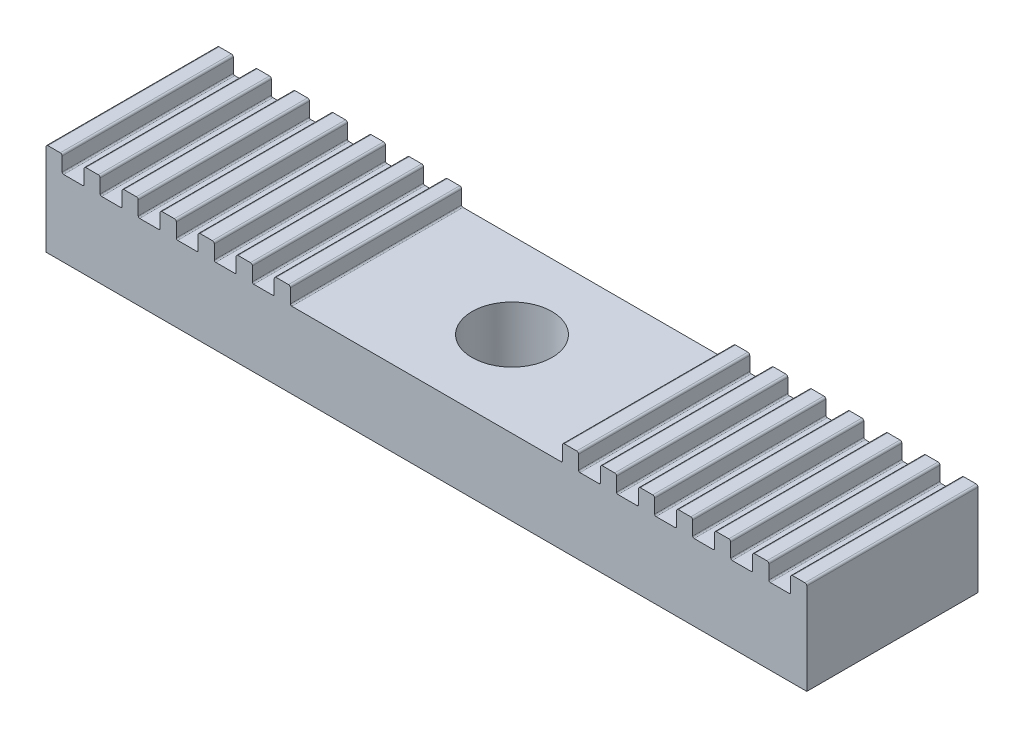
SolidWorks part; units mm, degrees
material "6061-T6 (SS)"
ref_plane "Front Plane" through (0, 0, 0) normal (0, 0, 1) x (1, 0, 0)
ref_plane "Top Plane" through (0, 0, 0) normal (0, 1, 0) x (1, 0, 0)
ref_plane "Right Plane" through (0, 0, 0) normal (1, 0, 0) x (0, 0, -1)
sketch "BaseS" plane through (0, 0, 0) normal (0, 1, 0) x (1, 0, 0)
  line L1 (-20, 4.5) -> (20, 4.5)
  line L2 (-20, 4.5) -> (-20, -4.5)
  line L3 (-20, -4.5) -> (20, -4.5)
  line L4 (20, 4.5) -> (20, -4.5)
  line L5 (-20, 4.5) -> (20, -4.5) construction
  line L6 (-20, -4.5) -> (20, 4.5) construction
  point P0 (0, 0)
  dimension "Width" = 9
  dimension "Length" = 40
extrude "Base" add sketch "BaseS" along normal blind 4
sketch "ToothProfileNestWallS" plane through (0, 0, 0) normal (0, 0, 1) x (1, 0, 0)
  line L0 (-19.075, 4) -> (-20.075, 4)
  line L1 (-20, 4) -> (20, 4) construction
  line L2 (-20, 4.075) -> (-20, 4.8)
  line L3 (-19.9, 4.9) -> (-19.25, 4.9)
  line L4 (-19.15, 4.075) -> (-19.15, 4.8)
  line L5 (-19.575, 4) -> (-19.575, 4.9) construction
  line L6 (-20, 4.075) -> (-20, 4) construction
  arc A0 (-20.075, 4) -> (-20, 4.075) centre (-20.075, 4.075) ccw
  arc A1 (-19.9, 4.9) -> (-20, 4.8) centre (-19.9, 4.8) ccw
  arc A2 (-19.25, 4.9) -> (-19.15, 4.8) centre (-19.25, 4.8) cw
  arc A3 (-19.075, 4) -> (-19.15, 4.075) centre (-19.075, 4.075) cw
  point P16 (0, 0)
  dimension "R2" = 0.1
  dimension "D1" = 0.85
  dimension "Height" = 0.9
  dimension "RefTopWidth" = 0.85
  dimension "TopWidthControl" = 0.075
extrude "ToothProfileNestWall" add sketch "ToothProfileNestWallS" along normal up to surface (4.5 mm away) and the other way up to surface (4.5 mm away) up to face at (0, 2, 4.5) other way up to face at (0, 2, -4.5)
pattern_linear "TPNWLP" count 7 spacing 2 along (1, 0, 0) of "ToothProfileNestWall"
sketch "TPFilletCutS" plane through (0, 0, 0) normal (0, 0, 1) x (1, 0, 0)
  line L0 (-20, 4) -> (-20, 0) construction
  line L1 (-20.075, 4) -> (-20, 4)
  line L2 (-20.075, 4) -> (-20.075, 4.075)
  line L3 (-20.075, 4.075) -> (-20, 4.075)
  line L5 (-20, 4.075) -> (-20, 4.8) construction
  line L6 (-20, 4) -> (-20, 4.075)
extrude "TPFilletCut" cut sketch "TPFilletCutS" against normal through all both and the other way through all
mirror "TPNWSetHM" about plane through (0, 0, 0) normal (1, 0, 0) of "TPFilletCut", "ToothProfileNestWall", "TPNWLP"
hole_wizard "M4 Clearance Hole1" positions "Sketch3" profile "Sketch4" hole size "M4" standard "ANSI Metric" end condition through all
sketch "Sketch3" plane through (0, 0, 0) normal (0, -1, 0) x (-1, 0, 0)
  point P0 (0, 0)
sketch "Sketch4" plane through (0, 0, 0) normal (1, 0, 0) x (0, 0, -1)
  line L0 (0, 0) -> (0, 4.9)
  line L1 (0, 4.9) -> (2.1, 4.9)
  line L2 (2.1, 4.9) -> (2.1, 0.15)
  line L3 (2.1, 0.15) -> (2.25, 0)
  line L5 (2.25, 0) -> (0, 0)
  line L6 (-2.1, 0.15) -> (-2.25, 0) construction
  line L11 (0, -6.35) -> (0, 107.95) construction
  dimension "Thru Hole Dia." = 4.2
  dimension "Thru Hole Depth" = 4.9
  dimension "Near C'Sink Dia." = 4.5
  dimension "Near C'Sink Angle" = 90
